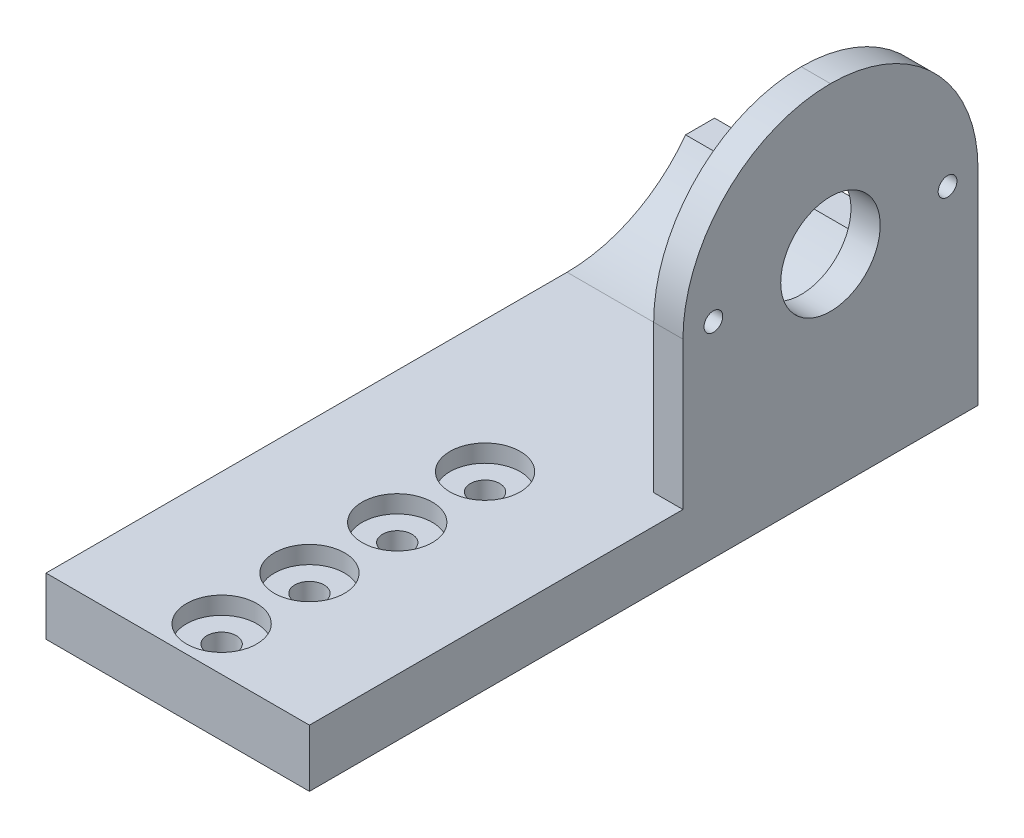
SolidWorks part; units mm, degrees
ref_plane "Front Plane" through (0, 0, 0) normal (0, 0, 1) x (1, 0, 0)
ref_plane "Top Plane" through (0, 0, 0) normal (0, 1, 0) x (1, 0, 0)
ref_plane "Right Plane" through (0, 0, 0) normal (1, 0, 0) x (0, 0, -1)
sketch "Sketch1" plane through (0, 0, 0) normal (0, 1, 0) x (1, 0, 0)
  line L1 (0, 0) -> (57.15, 0)
  line L2 (0, 0) -> (0, 145.034)
  line L3 (0, 145.034) -> (57.15, 145.034)
  line L4 (57.15, 0) -> (57.15, 145.034)
  dimension "D1" = 57.15
  dimension "D2" = 145.034
extrude "Boss-Extrude1" add sketch "Sketch1" along normal blind 25.4
sketch "Sketch3" plane through (57.15, 0, 0) normal (1, 0, 0) x (0, 0, -1)
  line L0 (0, 0) -> (145.034, 0) construction
  line L1 (145.034, 25.4) -> (145.034, 0) construction
  circle A0 centre (113.03, 44.45) radius 32.004
  dimension "D1" = 64.008
  dimension "D2" = 44.45
  dimension "D3" = 32.004
extrude "Cut-Extrude2" cut sketch "Sketch3" against normal through all
sketch "Sketch4" plane through (0, 0, 0) normal (0, -1, 0) x (-1, 0, 0)
  line L0 (0, 0) -> (-57.15, 0) construction
  line L1 (-57.15, 0) -> (-57.15, 145.034) construction
  circle A0 centre (-28.575, 9.525) radius 3.175
  circle A1 centre (-28.575, 28.575) radius 3.175
  circle A2 centre (-28.575, 47.625) radius 3.175
  circle A3 centre (-28.575, 66.675) radius 3.175
  dimension "D1" = 6.35
  dimension "D2" = 6.35
  dimension "D3" = 6.35
  dimension "D4" = 6.35
  dimension "D5" = 19.05
  dimension "D6" = 19.05
  dimension "D7" = 19.05
  dimension "D8" = 9.525
  dimension "D9" = 28.575
  dimension "D10" = 28.575
  dimension "D11" = 28.575
  dimension "D12" = 28.575
extrude "Cut-Extrude3" cut sketch "Sketch4" against normal through all
sketch "Sketch7" plane through (0, 0, 0) normal (0, -1, 0) x (1, 0, 0)
  line L0 (57.15, 0) -> (57.15, -145.034) construction
  line L1 (57.15, -81.026) -> (50.8, -81.026)
  line L2 (57.15, -81.026) -> (57.15, -145.034)
  line L3 (57.15, -145.034) -> (50.8, -145.034)
  line L4 (50.8, -81.026) -> (50.8, -145.034)
  line L8 (57.15, -145.034) -> (0, -145.034) construction
  dimension "D1" = 6.35
  dimension "D2" = 64.008
  dimension "D3" = 0
extrude "Boss-Extrude2" add sketch "Sketch7" against normal blind 76.454
fillet "Fillet1" radius 32.004 2 edges at (53.975, 76.454, -145.034) (53.975, 76.454, -81.026)
sketch "Sketch9" plane through (50.8, 0, 0) normal (-1, 0, 0) x (0, 0, 1)
  circle A1 centre (-113.03, 44.45) radius 10.795
  circle A2 centre (-138.43, 44.45) radius 2.032
  circle A3 centre (-87.63, 44.45) radius 2.032
  point P5 (-123.4328, 62.559)
  point P16 (0, 0)
  dimension "D1" = 21.59
  dimension "D4" = 4.064
  dimension "D5" = 4.064
  dimension "D2" = 25.4
  dimension "D3" = 25.4
  dimension "D6" = 32.004
  dimension "D7" = 32.004
  dimension "D8" = 32.004
  dimension "D9" = 32.004
extrude "Cut-Extrude5" cut sketch "Sketch9" against normal blind 76.454
sketch "Sketch10" plane through (0, 25.4, 0) normal (0, 1, 0) x (1, 0, 0)
  line L1 (50.8, 113.03) -> (0, 113.03)
  line L2 (50.8, 113.03) -> (50.8, 81.026)
  line L3 (50.8, 0) -> (0, 0)
  line L4 (0, 113.03) -> (0, 0)
  line L5 (57.15, 81.026) -> (50.8, 81.026)
  line L6 (57.15, 81.026) -> (57.15, 0)
  line L7 (57.15, 0) -> (50.8, 0)
extrude "Cut-Extrude7" cut sketch "Sketch10" against normal blind 12.954
sketch "Sketch11" plane through (0, 12.446, 0) normal (0, 1, 0) x (1, 0, 0)
  circle A0 centre (28.575, 66.675) radius 7.62
  circle A1 centre (28.575, 47.625) radius 7.62
  circle A2 centre (28.575, 28.575) radius 7.62
  circle A3 centre (28.575, 9.525) radius 7.62
  dimension "D1" = 15.24
  dimension "D2" = 15.24
  dimension "D3" = 15.24
  dimension "D4" = 15.24
extrude "Cut-Extrude8" cut sketch "Sketch11" against normal blind 3.81
